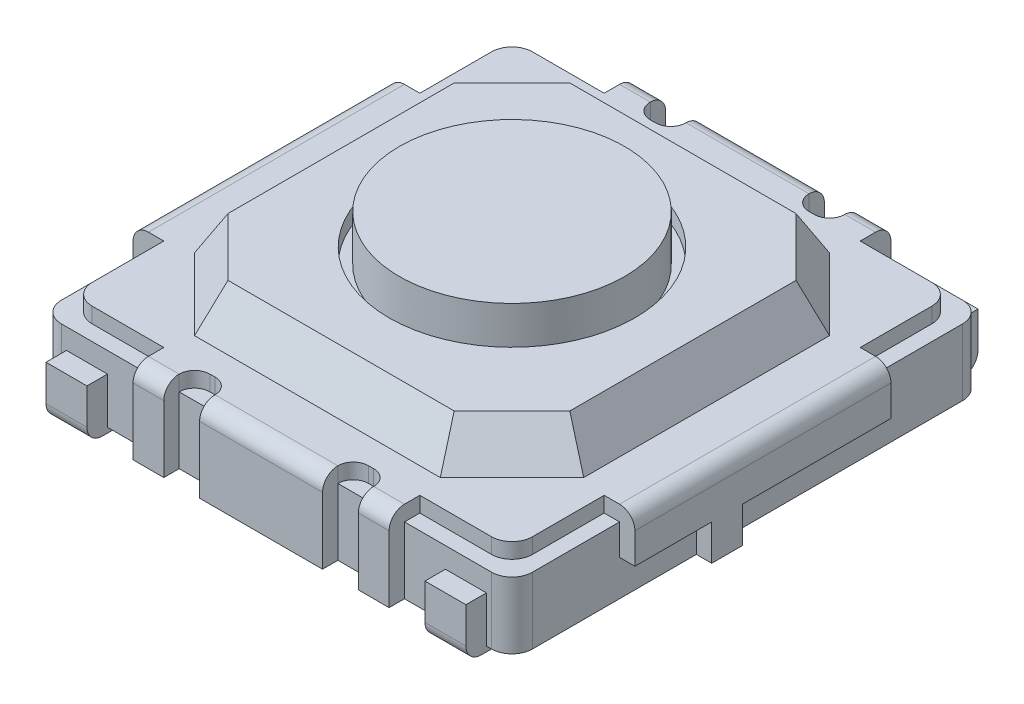
SolidWorks part; units mm, degrees
ref_plane "Front Plane" through (0, 0, 0) normal (0, 0, 1) x (1, 0, 0)
ref_plane "Top Plane" through (0, 0, 0) normal (0, 1, 0) x (1, 0, 0)
ref_plane "Right Plane" through (0, 0, 0) normal (1, 0, 0) x (0, 0, -1)
sketch "Sketch1" plane through (0, 0, 0) normal (0, 1, 0) x (1, 0, 0)
  line L0 (-1.9, -1.2) -> (-1.2, -1.9)
  line L1 (-2.3, 2.3) -> (2.3, 2.3)
  line L2 (-2.3, 2.3) -> (-2.3, -2.3)
  line L3 (-2.3, -2.3) -> (2.3, -2.3)
  line L4 (2.3, 2.3) -> (2.3, -2.3)
  line L5 (-1.9, 1.9) -> (-1.2, 1.9) construction
  line L6 (-1.9, 1.9) -> (-1.9, 1.2) construction
  line L7 (-1.9, -1.9) -> (-1.2, -1.9) construction
  line L8 (1.9, 1.9) -> (1.9, 1.2) construction
  line L9 (-1.7, 1.7) -> (-1.1172, 1.7) construction
  line L10 (-1.7, 1.7) -> (-1.7, 1.1172) construction
  line L11 (-1.7, -1.7) -> (-1.1172, -1.7) construction
  line L12 (1.7, 1.7) -> (1.7, 1.1172) construction
  line L13 (-1.7, -1.1172) -> (-1.1172, -1.7)
  line L14 (-1.7, 1.1172) -> (-1.1172, 1.7)
  line L15 (-1.9, 1.2) -> (-1.2, 1.9)
  line L16 (1.1172, 1.7) -> (1.7, 1.1172)
  line L17 (1.2, 1.9) -> (1.9, 1.2)
  line L18 (1.1172, -1.7) -> (1.7, -1.1172)
  line L19 (1.2, -1.9) -> (1.9, -1.2)
  line L20 (-1.9, -1.2) -> (-1.9, -1.9) construction
  line L21 (-1.9, 1.2) -> (-1.9, -1.2)
  line L22 (-1.7, -1.1172) -> (-1.7, -1.7) construction
  line L23 (-1.7, 1.1172) -> (-1.7, -1.1172)
  line L24 (-1.1172, 1.7) -> (1.1172, 1.7)
  line L25 (1.7, 1.1172) -> (1.7, -1.1172)
  line L26 (1.1172, 1.7) -> (1.7, 1.7) construction
  line L27 (1.7, -1.1172) -> (1.7, -1.7) construction
  line L28 (1.1172, -1.7) -> (1.7, -1.7) construction
  line L29 (-1.1172, -1.7) -> (1.1172, -1.7)
  line L30 (-1.2, -1.9) -> (1.2, -1.9)
  line L31 (1.2, -1.9) -> (1.9, -1.9) construction
  line L32 (1.9, -1.2) -> (1.9, -1.9) construction
  line L33 (1.9, 1.2) -> (1.9, -1.2)
  line L34 (1.2, 1.9) -> (1.9, 1.9) construction
  line L35 (-1.2, 1.9) -> (1.2, 1.9)
  line L36 (-1.1, 0) -> (1.1, 0) construction
  line L37 (0, -1.1) -> (0, 1.1) construction
  line L38 (-2.45, 1.25) -> (-2.45, -1.25)
  line L39 (-2.45, -1.25) -> (-2.15, -1.25)
  line L40 (-2.15, -1.25) -> (-2.15, -2.15)
  line L41 (-2.15, -2.15) -> (-1.25, -2.15)
  line L42 (-1.25, -2.15) -> (-1.25, -2.45)
  line L43 (-1.25, -2.45) -> (-0.95, -2.45)
  line L44 (-0.95, -2.45) -> (-0.95, -2.15)
  line L45 (-0.95, -2.15) -> (-0.6, -2.15)
  line L46 (-0.6, -2.15) -> (-0.6, -2.45)
  line L47 (-0.6, -2.45) -> (0.6, -2.45)
  line L48 (0.6, -2.15) -> (0.6, -2.45)
  line L49 (0.95, -2.15) -> (0.6, -2.15)
  line L50 (0.95, -2.45) -> (0.95, -2.15)
  line L51 (1.25, -2.45) -> (0.95, -2.45)
  line L52 (1.25, -2.15) -> (1.25, -2.45)
  line L53 (2.15, -2.15) -> (1.25, -2.15)
  line L54 (2.15, -1.25) -> (2.15, -2.15)
  line L55 (2.45, -1.25) -> (2.15, -1.25)
  line L56 (2.45, 1.25) -> (2.45, -1.25)
  line L57 (-2.45, 1.25) -> (-2.15, 1.25)
  line L58 (-2.15, 1.25) -> (-2.15, 2.15)
  line L59 (-2.15, 2.15) -> (-1.25, 2.15)
  line L60 (-1.25, 2.15) -> (-1.25, 2.45)
  line L61 (-1.25, 2.45) -> (-0.95, 2.45)
  line L62 (-0.95, 2.45) -> (-0.95, 2.15)
  line L63 (-0.95, 2.15) -> (-0.6, 2.15)
  line L64 (-0.6, 2.15) -> (-0.6, 2.45)
  line L65 (-0.6, 2.45) -> (0.6, 2.45)
  line L66 (0.6, 2.15) -> (0.6, 2.45)
  line L67 (0.95, 2.15) -> (0.6, 2.15)
  line L68 (0.95, 2.45) -> (0.95, 2.15)
  line L69 (1.25, 2.45) -> (0.95, 2.45)
  line L70 (1.25, 2.15) -> (1.25, 2.45)
  line L71 (2.15, 2.15) -> (1.25, 2.15)
  line L72 (2.15, 1.25) -> (2.15, 2.15)
  line L73 (2.45, 1.25) -> (2.15, 1.25)
  circle A0 centre (0, 0) radius 1.1
  circle A1 centre (0, 0) radius 1.2
  point P48 (0, -2.45)
  point P58 (-2.45, 0)
  point P75 (2.45, 0)
  dimension "D5" = 2.2
  dimension "D6" = 2.4
  dimension "D1" = 4.6
  dimension "D2" = 1.9
  dimension "D3" = 2.3
  dimension "D4" = 2.3
  dimension "D7" = 3.8
  dimension "D8" = 3.4
  dimension "D9" = 1.9
  dimension "D10" = 1.7
  dimension "D11" = 1.7
  dimension "D12" = 0.2
  dimension "D13" = 0.2
  dimension "D14" = 0.2
  dimension "D15" = 0.2
  dimension "D16" = 0.2
  dimension "D17" = 0.2
  dimension "D18" = 135
  dimension "D19" = 2.4
  dimension "D20" = 1.2
  dimension "D21" = 0.15
  dimension "D22" = 0.15
  dimension "D23" = 1.25
  dimension "D24" = 0.6
  dimension "D25" = 0.15
  dimension "D26" = 0.15
  dimension "D27" = 1.25
  dimension "D28" = 0.3
extrude "Extrude1" add sketch "Sketch1" along normal blind 0.65 contours L4 L3 L2 L1
extrude "Extrude2" add sketch "Sketch1<3>" along normal blind 0.8 contours L47 L48 L49 L50 L51 L52 L53 L54 L55 L56 L73 L72 L71 L70 L69 L68 L67 L66 L65 L64 L63 L62 L61 L60 L59 L58 L57 L38 L39 L40 L41 L42 L43 L44 L45 L46
sketch "Sketch1<3>" plane through (0, 0, 0) normal (0, 1, 0) x (1, 0, 0) same geometry as "Sketch1"
sketch "Sketch2" plane through (0, 0.8, 0) normal (0, 1, 0) x (-1, 0, 0)
  line L32 (1.9, 1.2) -> (1.2, 1.9)
  line L33 (1.2, 1.9) -> (-1.2, 1.9)
  line L34 (-1.2, 1.9) -> (-1.9, 1.2)
  line L35 (-1.9, 1.2) -> (-1.9, -1.2)
  line L36 (-1.9, -1.2) -> (-1.2, -1.9)
  line L37 (-1.2, -1.9) -> (1.2, -1.9)
  line L38 (1.2, -1.9) -> (1.9, -1.2)
  line L39 (1.9, -1.2) -> (1.9, 1.2)
  line L40 (1.9, 1.2) -> (1.2, 1.9)
  line L41 (1.2, 1.9) -> (-1.2, 1.9)
  line L42 (-1.2, 1.9) -> (-1.9, 1.2)
  line L43 (-1.9, 1.2) -> (-1.9, -1.2)
  line L44 (-1.9, -1.2) -> (-1.2, -1.9)
  line L45 (-1.2, -1.9) -> (1.2, -1.9)
  line L46 (1.2, -1.9) -> (1.9, -1.2)
  line L47 (1.9, -1.2) -> (1.9, 1.2)
  dimension "D5" = 0
extrude "Extrude3" add sketch "Sketch2" along normal blind 0.4 draft 30
extrude "Extrude4" add sketch "Sketch1<4>" along normal blind 1.5 contours A0
sketch "Sketch1<4>" plane through (0, 0, 0) normal (0, 1, 0) x (1, 0, 0) same geometry as "Sketch1"
sketch "Sketch3" plane through (0, 1.2, 0) normal (0, 1, 0) x (-1, 0, 0)
  circle A1 centre (0, 0) radius 1.2
  circle A2 centre (0, 0) radius 1.2
  circle A3 centre (0, 0) radius 1.1
  circle A4 centre (0, 0) radius 1.1
  dimension "D1" = 0
  dimension "D2" = 0
extrude "Cut-Extrude1" cut sketch "Sketch3" against normal blind 0.15
sketch "Sketch4" plane through (2.45, 0, 0) normal (1, 0, 0) x (0, 0, -1)
  line L1 (-1.25, 0.35) -> (-0.5, 0.35)
  line L2 (-1.25, 0.35) -> (-1.25, 0)
  line L3 (-1.25, 0) -> (-0.5, 0)
  line L4 (-0.5, 0.35) -> (-0.5, 0)
  line L5 (1.25, 0) -> (-1.25, 0) construction
  line L7 (-0.2, 0) -> (1.25, 0)
  line L8 (-0.2, 0) -> (-0.2, 0.35)
  line L9 (-0.2, 0.35) -> (1.25, 0.35)
  line L10 (1.25, 0) -> (1.25, 0.35)
  line L11 (-1.2, 0.8) -> (1.2, 0.8) construction
  dimension "D1" = 0.3
  dimension "D2" = 0.2
  dimension "D3" = 0.45
extrude "Cut-Extrude2" cut sketch "Sketch4" against normal blind 0.15
sketch "Sketch5" plane through (-2.45, 0, 0) normal (-1, 0, 0) x (0, 0, 1)
  line L0 (0, -0.2978) -> (0, -0.643) construction
  line L1 (-1.25, 0) -> (-1.25, 0.35)
  line L2 (-0.5, 0) -> (-1.25, 0)
  line L3 (-0.5, 0.35) -> (-0.5, 0)
  line L4 (-1.25, 0.35) -> (-0.5, 0.35)
  line L5 (-0.2, 0) -> (-0.2, 0.35)
  line L6 (-0.2, 0.35) -> (1.25, 0.35)
  line L7 (1.25, 0.35) -> (1.25, 0)
  line L12 (1.25, 0) -> (-0.2, 0)
extrude "Cut-Extrude3" cut sketch "Sketch5" against normal blind 0.15
sketch "Sketch6" plane through (0, 0, 0) normal (0, 1, 0) x (1, 0, 0)
  line L1 (2.05, 2.5) -> (1.85, 2.5)
  line L2 (2.05, 2.5) -> (2.05, 1.75)
  line L3 (2.05, 1.75) -> (1.65, 1.75)
  line L4 (1.65, 2.5) -> (1.65, 1.75)
  line L5 (1.85, 2.5) -> (1.65, 2.5)
  line L6 (-1.4778, 0) -> (-0.6439, 0) construction
  line L7 (0, -1.5802) -> (0, -0.7556) construction
  line L8 (-2.05, 2.5) -> (-1.85, 2.5)
  line L9 (-1.85, 2.5) -> (-1.65, 2.5)
  line L10 (-1.65, 2.5) -> (-1.65, 1.75)
  line L11 (-2.05, 1.75) -> (-1.65, 1.75)
  line L12 (-2.05, 2.5) -> (-2.05, 1.75)
  line L13 (2.05, -2.5) -> (1.85, -2.5)
  line L14 (1.85, -2.5) -> (1.65, -2.5)
  line L15 (1.65, -2.5) -> (1.65, -1.75)
  line L16 (2.05, -1.75) -> (1.65, -1.75)
  line L17 (2.05, -2.5) -> (2.05, -1.75)
  line L18 (-1.85, -2.5) -> (-1.65, -2.5)
  line L19 (-2.05, -2.5) -> (-1.85, -2.5)
  line L20 (-2.05, -2.5) -> (-2.05, -1.75)
  line L21 (-2.05, -1.75) -> (-1.65, -1.75)
  line L22 (-1.65, -2.5) -> (-1.65, -1.75)
  dimension "D1" = 2.5
  dimension "D2" = 1.85
  dimension "D3" = 0.4
  dimension "D4" = 1.75
extrude "Extrude5" add sketch "Sketch6" along normal blind 0.45 and the other way blind 0.05
fillet "Fillet1" radius 0.2 8 edges at (-2.15, 0.725, -2.15) (-2.3, 0.325, -2.3) (2.15, 0.725, -2.15) (2.3, 0.325, -2.3) (2.15, 0.725, 2.15) (2.3, 0.325, 2.3) (-2.15, 0.725, 2.15) (-2.3, 0.325, 2.3)
fillet "Fillet2" radius 0.15 8 edges at (0.95, 0.725, 2.15) (0.6, 0.725, 2.15) (-0.6, 0.725, 2.15) (-0.95, 0.725, 2.15) (-0.95, 0.725, -2.15) (-0.6, 0.725, -2.15) (0.6, 0.725, -2.15) (0.95, 0.725, -2.15)
fillet "Fillet3" radius 0.15 12 edges at (1.85, -0.05, 2.5) (-1.85, -0.05, 2.5) (1.85, -0.05, -2.5) (-1.85, -0.05, -2.5) (-2.45, 0.8, 0) (-1.1, 0.8, -2.45) (0, 0.8, -2.45) (1.1, 0.8, -2.45) (2.45, 0.8, 0) (1.1, 0.8, 2.45) (-1.1, 0.8, 2.45) (0, 0.8, 2.45)
ref_plane "Board Plane" through (0, -0.05, 0) normal (0, 1, 0) x (-1, 0, 0)
sketch "Component_Outline" plane through (0, -0.05, 0) normal (0, 1, 0) x (-1, 0, 0)
  line L0 (2.3, 1.25) -> (2.45, 1.25)
  line L1 (2.45, 1.25) -> (2.45, -1.25)
  line L2 (2.45, -1.25) -> (2.3, -1.25)
  line L3 (2.3, -1.25) -> (2.3, -2.3)
  line L4 (2.3, -2.3) -> (2.05, -2.3)
  line L5 (2.05, -2.3) -> (2.05, -2.5)
  line L6 (2.05, -2.5) -> (1.65, -2.5)
  line L7 (1.65, -2.5) -> (1.65, -2.3)
  line L8 (1.65, -2.3) -> (1.25, -2.3)
  line L9 (1.25, -2.3) -> (1.25, -2.45)
  line L10 (1.25, -2.45) -> (0.95, -2.45)
  line L11 (0.95, -2.45) -> (0.95, -2.3)
  line L12 (0.95, -2.3) -> (0.6, -2.3)
  line L13 (0.6, -2.3) -> (0.6, -2.45)
  line L14 (0.6, -2.45) -> (-0.6, -2.45)
  line L15 (-0.6, -2.45) -> (-0.6, -2.3)
  line L16 (-0.6, -2.3) -> (-0.95, -2.3)
  line L17 (-0.95, -2.3) -> (-0.95, -2.45)
  line L18 (-0.95, -2.45) -> (-1.25, -2.45)
  line L19 (-1.25, -2.45) -> (-1.25, -2.3)
  line L20 (-1.25, -2.3) -> (-1.65, -2.3)
  line L21 (-1.65, -2.3) -> (-1.65, -2.5)
  line L22 (-1.65, -2.5) -> (-2.05, -2.5)
  line L23 (-2.05, -2.5) -> (-2.05, -2.3)
  line L24 (-2.05, -1.75) -> (-2.05, -2.35) construction
  line L25 (-2.05, -2.3) -> (-2.3, -2.3)
  line L26 (-2.3, -2.3) -> (-2.3, -1.25)
  line L27 (-2.3, -1.25) -> (-2.45, -1.25)
  line L28 (-2.45, -1.25) -> (-2.45, 1.25)
  line L29 (-2.05, -2.3) -> (-2.1, -2.3) construction
  line L30 (2.3, 1.25) -> (2.3, 2.3)
  line L31 (2.3, 2.3) -> (2.05, 2.3)
  line L32 (2.05, 2.3) -> (2.05, 2.5)
  line L33 (2.05, 2.5) -> (1.65, 2.5)
  line L34 (1.65, 2.5) -> (1.65, 2.3)
  line L35 (1.65, 2.3) -> (1.25, 2.3)
  line L36 (1.25, 2.3) -> (1.25, 2.45)
  line L37 (1.25, 2.45) -> (0.95, 2.45)
  line L38 (0.95, 2.45) -> (0.95, 2.3)
  line L39 (0.95, 2.3) -> (0.6, 2.3)
  line L40 (0.6, 2.3) -> (0.6, 2.45)
  line L41 (0.6, 2.45) -> (-0.6, 2.45)
  line L42 (-0.6, 2.45) -> (-0.6, 2.3)
  line L43 (-0.6, 2.3) -> (-0.95, 2.3)
  line L44 (-0.95, 2.3) -> (-0.95, 2.45)
  line L45 (-0.95, 2.45) -> (-1.25, 2.45)
  line L46 (-1.25, 2.45) -> (-1.25, 2.3)
  line L47 (-1.25, 2.3) -> (-1.65, 2.3)
  line L48 (-1.65, 2.3) -> (-1.65, 2.5)
  line L49 (-1.65, 2.5) -> (-2.05, 2.5)
  line L50 (-2.05, 2.5) -> (-2.05, 2.3)
  line L51 (-2.05, 2.35) -> (-2.05, 1.75) construction
  line L52 (-2.05, 2.3) -> (-2.3, 2.3)
  line L53 (-2.05, 2.3) -> (-2.1, 2.3) construction
  line L54 (-2.3, 0.5) -> (-2.3, 2.1) construction
  line L55 (-2.3, 1.25) -> (-2.45, 1.25)
  line L56 (-2.3, 1.25) -> (-2.3, 2.3)
